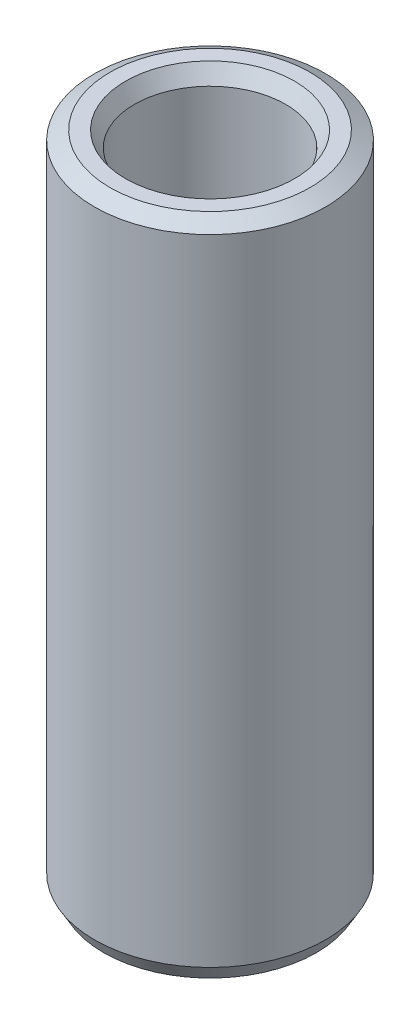
SolidWorks part; units mm, degrees
ref_plane "Front Plane" through (0, 0, 0) normal (0, 0, 1) x (1, 0, 0)
ref_plane "Top Plane" through (0, 0, 0) normal (0, 1, 0) x (1, 0, 0)
ref_plane "Right Plane" through (0, 0, 0) normal (1, 0, 0) x (0, 0, -1)
sketch "Sketch1" plane through (0, 0, 0) normal (0, 1, 0) x (1, 0, 0)
  circle A0 centre (0, 0) radius 42.5
  dimension "SLEEVE_OD" = 85
extrude "Boss-Extrude1" add sketch "Sketch1" along normal blind 242.4509
sketch "Sketch2" plane through (0, 0, 0) normal (0, 1, 0) x (1, 0, 0)
  circle A0 centre (0, 0) radius 27.7868
  dimension "BORE_D" = 55.5736
extrude "Cut-Extrude1" cut sketch "Sketch2" along normal through all
chamfer "Chamfer1" distance 3.3039 angle 60 4 edges at (0, 242.4509, 27.7868) (0, 0, 27.7868) (0, 0, 42.5) (0, 242.4509, 42.5) first distance on face at (0, 242.4509, 27.7868) first distance on face at (0, 0, 27.7868) first distance on face at (0, 242.4509, 42.5)
